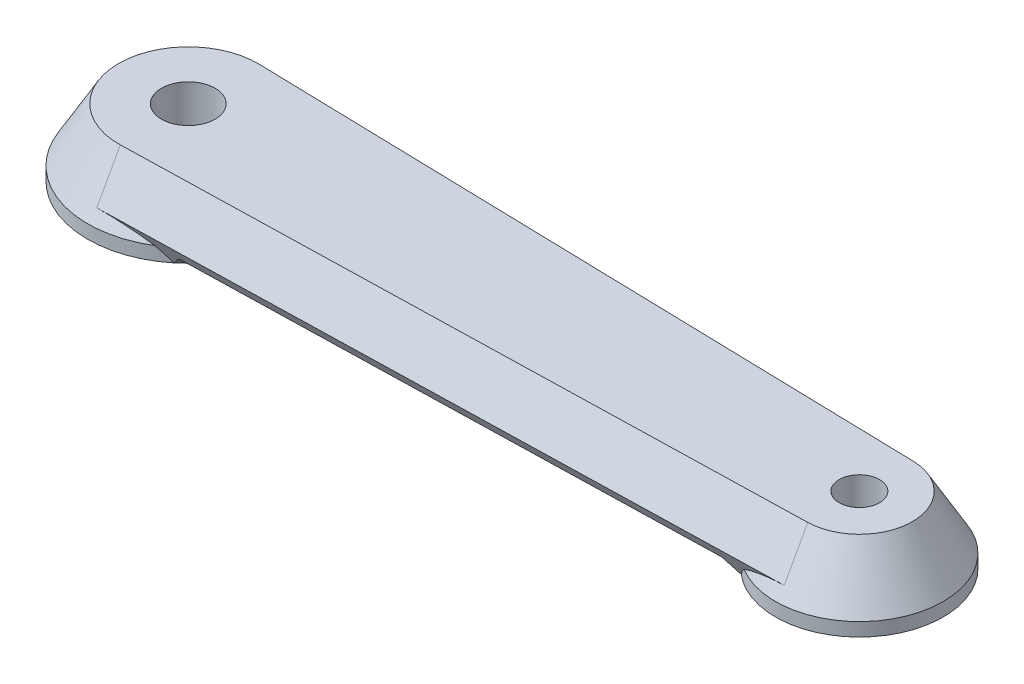
SolidWorks part; units mm, degrees
ref_plane "Front Plane" through (0, 0, 0) normal (0, 0, 1) x (1, 0, 0)
ref_plane "Top Plane" through (0, 0, 0) normal (0, 1, 0) x (1, 0, 0)
ref_plane "Right Plane" through (0, 0, 0) normal (1, 0, 0) x (0, 0, -1)
sketch "Sketch1" plane through (0, 0, 0) normal (0, 1, 0) x (1, 0, 0)
  line L0 (0, 0) -> (500, 0) construction
  circle A0 centre (0, 0) radius 75
  circle A1 centre (500, 0) radius 62.5
  dimension "D1" = 150
  dimension "D2" = 125
  dimension "D3" = 500
extrude "Boss-Extrude1" add sketch "Sketch1" along normal blind 10
sketch "Sketch3" plane through (0, 10, 0) normal (0, 1, 0) x (1, 0, 0)
  line L0 (1.875, 74.9766) -> (501.5625, 62.4805)
  line L2 (1.875, -74.9766) -> (501.5625, -62.4805)
  circle A0 centre (500, 0) radius 62.5 construction
  circle A1 centre (0, 0) radius 75 construction
  arc A2 (501.5625, -62.4805) -> (501.5625, 62.4805) centre (500, 0) ccw
  arc A3 (1.875, 74.9766) -> (1.875, -74.9766) centre (0, 0) ccw
  arc A4 (1.875, -74.9766) -> (1.875, 74.9766) centre (0, 0) ccw construction
  arc A5 (501.5625, 62.4805) -> (501.5625, -62.4805) centre (500, 0) ccw construction
extrude "Boss-Extrude3" add sketch "Sketch3" along normal blind 40 draft 30
sketch "Sketch4" plane through (0, 0, 0) normal (0, -1, 0) x (1, 0, 0)
  circle A0 centre (0, 0) radius 20
  circle A1 centre (500, 0) radius 15
  circle A2 centre (500, 0) radius 62.5 construction
  dimension "D1" = 40
  dimension "D2" = 30
extrude "Cut-Extrude1" cut sketch "Sketch4" against normal through all both and the other way through all
chamfer "Chamfer1" distance 10 angle 60 2 edges at (251.7188, 10, 68.7285) (251.7188, 10, -68.7285)
chamfer "Chamfer2" distance 10 angle 45 2 edges at (437.5, 10, 0) (75, 10, 0)
